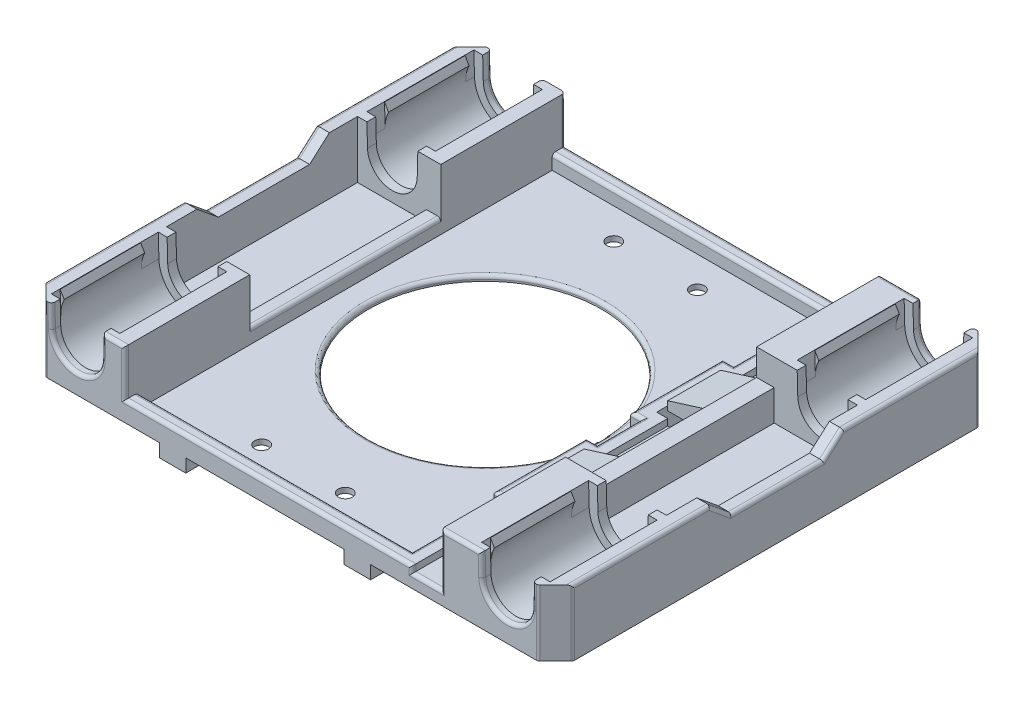
SolidWorks part; units mm, degrees
ref_plane "Front" through (0, 0, 0) normal (0, 0, 1) x (1, 0, 0)
ref_plane "Top" through (0, 0, 0) normal (0, 1, 0) x (1, 0, 0)
ref_plane "Right" through (0, 0, 0) normal (1, 0, 0) x (0, 0, -1)
sketch "Sketch1" plane through (0, 0, 0) normal (0, 1, 0) x (1, 0, 0)
  line L1 (-62.38, 50) -> (62.38, 50)
  line L2 (-62.38, 50) -> (-62.38, -50)
  line L3 (-62.38, -50) -> (62.38, -50)
  line L4 (62.38, 50) -> (62.38, -50)
  dimension "D1" = 124.76
  dimension "D2" = 100
  dimension "6" = 62.38
  dimension "D4" = 50
extrude "Boss-Extrude1" add sketch "Sketch1" along normal blind 20
sketch "Sketch2" plane through (0, 0, 50) normal (0, 0, 1) x (1, 0, 0)
  line L0 (-62.38, 0) -> (62.38, 0) construction
  line L1 (-62.38, 20) -> (-62.38, 0) construction
  line L2 (62.38, 20) -> (62.38, 0) construction
  circle A0 centre (-48.88, 10) radius 7.65
  circle A1 centre (48.88, 10) radius 7.65
  dimension "D2" = 15.3
  dimension "D3" = 15.3
  dimension "D1" = 13.5
  dimension "D4" = 10
  dimension "D5" = 10
  dimension "D6" = 13.5
  dimension "D7" = 97.76
extrude "Cut-Extrude1" cut sketch "Sketch2" against normal through all
sketch "Sketch4" plane through (-62.38, 0, 0) normal (-1, 0, 0) x (0, 0, 1)
  line L0 (-50, 20) -> (50, 20) construction
  line L1 (48, 2) -> (-48, 2)
  line L2 (48, 2) -> (48, 20)
  line L3 (48, 20) -> (-48, 20)
  line L4 (-48, 2) -> (-48, 20)
  line L5 (-50, 0) -> (50, 0) construction
  line L6 (50, 2.35) -> (50, 17.65) construction
  line L9 (-50, 20) -> (-50, 0) construction
  dimension "D1" = 2
  dimension "D2" = 2
  dimension "D3" = 2
extrude "Cut-Extrude2" cut sketch "Sketch4" against normal blind 21.26
sketch "Sketch5" plane through (62.38, 0, 0) normal (1, 0, 0) x (0, 0, -1)
  line L0 (-50, 20) -> (50, 20) construction
  line L1 (-48, 2) -> (48, 2)
  line L2 (-48, 2) -> (-48, 20)
  line L3 (-48, 20) -> (48, 20)
  line L4 (48, 2) -> (48, 20)
  line L5 (-50, 0) -> (50, 0) construction
  line L6 (-50, 20) -> (-50, 0) construction
  line L7 (50, 20) -> (50, 0) construction
  dimension "D1" = 2
  dimension "D2" = 2
  dimension "D3" = 2
extrude "Cut-Extrude3" cut sketch "Sketch5" against normal blind 24.5
sketch "Sketch6" plane through (0, 0, 48) normal (0, 0, -1) x (-1, 0, 0)
  line L0 (41.12, 20) -> (62.38, 20) construction
  line L1 (37.88, 20) -> (59.88, 20)
  line L2 (37.88, 20) -> (37.88, 2)
  line L3 (37.88, 2) -> (59.88, 2)
  line L4 (59.88, 20) -> (59.88, 2)
  line L5 (41.12, 2) -> (62.38, 2) construction
  circle A0 centre (48.88, 10) radius 7.65 construction
  circle A1 centre (48.88, 10) radius 7.65
  dimension "D1" = 22
  dimension "D2" = 11
extrude "Boss-Extrude2" add sketch "Sketch6" along normal blind 24.3
mirror "Mirror1" about plane through (0, 0, 0) normal (0, 0, 1) of "Boss-Extrude2"
mirror "Mirror2" about plane through (0, 0, 0) normal (1, 0, 0) of "Mirror1", "Boss-Extrude2"
sketch "Sketch7" plane through (0, 0, 50) normal (0, 0, 1) x (1, 0, 0)
  line L0 (41.2326, 9.8) -> (40.9659, 20)
  line L2 (-62.38, 20) -> (62.38, 20) construction
  line L3 (40.9659, 20) -> (56.7941, 20)
  line L4 (56.7941, 20) -> (56.5274, 9.8)
  circle A1 centre (48.88, 10) radius 7.65 construction
  arc A2 (41.2326, 9.8) -> (56.5274, 9.8) centre (48.88, 10) ccw
  dimension "D1" = 0.2
  dimension "D2" = 0.2
extrude "Cut-Extrude4" cut sketch "Sketch7" against normal blind 4
mirror "Mirror3" about plane through (0, 0, 0) normal (1, 0, 0) of "Cut-Extrude4"
mirror "Mirror4" about plane through (0, 0, 0) normal (0, 0, 1) of "Mirror3", "Cut-Extrude4"
sketch "Sketch8" plane through (0, 0, -23.7) normal (0, 0, 1) x (1, 0, 0)
  line L0 (56.5274, 9.8) -> (56.7941, 20) construction
  line L1 (40.9659, 20) -> (41.2326, 9.8) construction
  line L2 (56.5274, 9.8) -> (56.7941, 20)
  line L3 (40.9659, 20) -> (41.2326, 9.8)
  line L4 (56.7941, 20) -> (40.9659, 20)
  arc A0 (41.2326, 9.8) -> (56.5274, 9.8) centre (48.88, 10) ccw construction
  arc A1 (41.2326, 9.8) -> (56.5274, 9.8) centre (48.88, 10) ccw
extrude "Cut-Extrude5" cut sketch "Sketch8" against normal blind 4
mirror "Mirror5" about plane through (0, 0, 0) normal (1, 0, 0) of "Cut-Extrude5"
mirror "Mirror6" about plane through (0, 0, 0) normal (0, 0, 1) of "Mirror5", "Cut-Extrude5"
sketch "Sketch10" plane through (0, 0, -46) normal (0, 0, -1) x (-1, 0, 0)
  line L0 (41.0992, 14.9025) -> (41.9993, 13.3435)
  line L1 (56.5274, 9.8) -> (56.7941, 20) construction
  line L2 (56.6608, 14.9025) -> (56.7941, 20)
  line L3 (56.7941, 20) -> (40.9659, 20)
  line L4 (40.9659, 20) -> (41.0992, 14.9025)
  line L5 (40.9659, 20) -> (41.2326, 9.8) construction
  line L7 (55.7607, 13.3435) -> (56.6608, 14.9025)
  arc A0 (56.5274, 9.8) -> (41.2326, 9.8) centre (48.88, 10) ccw construction
  arc A1 (55.7607, 13.3435) -> (41.9993, 13.3435) centre (48.88, 10) ccw
  dimension "D2" = 151.498
  dimension "D1" = 151.498
extrude "Cut-Extrude6" cut sketch "Sketch10" against normal through all both and the other way through all
mirror "Mirror7" about plane through (0, 0, 0) normal (1, 0, 0) of "Cut-Extrude6"
ref_plane "Plane6" through (0, 10, 0) normal (0, 1, 0) x (1, 0, 0)
sketch "Sketch11" [suppressed] plane through (0, 10, 0) normal (0, 1, 0) x (1, 0, 0)
  line L4 (42.7319, -46) -> (42.7319, -27.7)
  line L5 (42.7319, -46) -> (42.7319, -27.7)
  line L6 (41.1969, -27.7) -> (41.1969, -46)
  line L7 (42.7319, -27.7) -> (41.1969, -27.7)
  line L8 (42.7319, -27.7) -> (41.1969, -27.7)
  line L9 (41.1969, -46) -> (42.7319, -46)
  line L10 (41.1969, -27.7) -> (41.1969, -46)
  line L11 (41.1969, -46) -> (42.7319, -46)
  line L12 (56.5631, -46) -> (56.5631, -27.7)
  line L13 (56.5631, -27.7) -> (55.0281, -27.7)
  line L14 (55.0281, -27.7) -> (55.0281, -46)
  line L15 (55.0281, -46) -> (56.5631, -46)
  line L16 (56.5631, -46) -> (56.5631, -27.7)
  line L17 (56.5631, -27.7) -> (55.0281, -27.7)
  line L18 (55.0281, -27.7) -> (55.0281, -46)
  line L19 (55.0281, -46) -> (56.5631, -46)
  dimension "D1" = 0
  dimension "D2" = 0
extrude "Cut-Extrude7" [suppressed] cut sketch "Sketch11" against normal through all
mirror "Mirror8" [suppressed] about plane through (0, 0, 0) normal (1, 0, 0)
mirror "Mirror9" [suppressed] about plane through (0, 0, 0) normal (0, 0, 1)
sketch "Sketch12" plane through (0, 0, -50) normal (0, 0, -1) x (-1, 0, 0)
  line L2 (54.7948, 20.0523) -> (62.38, 20)
  line L3 (62.38, 20) -> (62.38, 0)
  line L4 (42.9652, 20.0523) -> (43.2319, 9.8523)
  line L5 (54.5281, 9.8523) -> (54.7948, 20.0523)
  line L6 (42.9652, 20.0523) -> (43.2319, 9.8523)
  line L7 (54.5281, 9.8523) -> (54.7948, 20.0523)
  line L8 (62.38, 0) -> (30.8026, 0)
  line L9 (-62.38, 0) -> (62.38, 0) construction
  line L10 (30.8026, 0) -> (30.8026, 20)
  line L11 (-40.9659, 20) -> (40.9659, 20) construction
  line L12 (30.8026, 20) -> (42.9652, 20.0523)
  arc A2 (43.2319, 9.8523) -> (54.5281, 9.8523) centre (48.88, 10) ccw
  arc A3 (43.2319, 9.8523) -> (54.5281, 9.8523) centre (48.88, 10) ccw
  dimension "D1" = 2
extrude "Boss-Extrude3" add sketch "Sketch12" against normal blind 2
mirror "Mirror10" about plane through (0, 0, 0) normal (1, 0, 0) of "Boss-Extrude3"
mirror "Mirror11" about plane through (0, 0, 0) normal (0, 0, 1) of "Boss-Extrude3", "Mirror10"
sketch "Sketch13" plane through (0, 0, 23.7) normal (0, 0, -1) x (-1, 0, 0)
  line L0 (54.7948, 20.0523) -> (54.5281, 9.8523) construction
  line L1 (43.2319, 9.8523) -> (42.9652, 20.0523) construction
  line L2 (54.7948, 20.0523) -> (54.5281, 9.8523)
  line L3 (43.2319, 9.8523) -> (42.9652, 20.0523)
  line L4 (56.7941, 20) -> (54.7948, 20.0523)
  line L5 (56.7941, 20) -> (59.88, 20)
  line L6 (59.88, 20) -> (59.88, 2)
  line L7 (41.12, 2) -> (59.88, 2) construction
  line L8 (59.88, 2) -> (35.5, 2)
  line L9 (35.5, 2) -> (35.5, 20)
  line L11 (35.5, 20) -> (42.9652, 20.0523)
  arc A0 (43.2319, 9.8523) -> (54.5281, 9.8523) centre (48.88, 10) ccw construction
  arc A1 (43.2319, 9.8523) -> (54.5281, 9.8523) centre (48.88, 10) ccw
extrude "Boss-Extrude4" add sketch "Sketch13" along normal blind 2
mirror "Mirror12" about plane through (0, 0, 0) normal (1, 0, 0) of "Boss-Extrude4"
mirror "Mirror13" about plane through (0, 0, 0) normal (0, 0, 1) of "Mirror12", "Boss-Extrude4"
sketch "Sketch14" plane through (0, 0, 0) normal (0, -1, 0) x (1, 0, 0)
  line L0 (59.88, 21.7) -> (59.88, 48) construction
  line L1 (59.88, -50) -> (59.88, 50)
  line L2 (-62.38, 50) -> (62.38, 50) construction
  line L3 (62.38, 50) -> (62.38, -50) construction
  line L4 (62.38, 50) -> (62.38, -50)
  line L5 (59.88, 50) -> (62.38, 50)
  line L6 (59.88, -50) -> (62.38, -50)
extrude "Cut-Extrude9" cut sketch "Sketch14" against normal through all
mirror "Mirror15" about plane through (0, 0, 0) normal (1, 0, 0) of "Cut-Extrude9"
sketch "Sketch15" plane through (0, 20, 0) normal (0, 1, 0) x (1, 0, 0)
  line L0 (33.88, -50) -> (33.88, 50)
  line L1 (-30.8026, -50) -> (30.8026, -50) construction
  line L2 (30.8026, 50) -> (-30.8026, 50) construction
  line L3 (59.88, -21.7) -> (59.88, 21.7) construction
  line L4 (27.38, -50) -> (27.38, 50)
  line L5 (27.38, 50) -> (33.88, 50)
  line L6 (33.88, -50) -> (27.38, -50)
  dimension "D1" = 26
  dimension "D2" = 6.5
extrude "Cut-Extrude10" cut sketch "Sketch15" against normal blind 17
sketch "Sketch16" plane through (0, 2, 0) normal (0, 1, 0) x (1, 0, 0)
  line L2 (-59.88, 21.7) -> (-59.88, -21.7)
  line L3 (-59.88, -21.7) -> (-56.7941, -21.7)
  line L4 (-41.12, -21.7) -> (-59.88, -21.7) construction
  line L5 (-59.88, 21.7) -> (-56.7941, 21.7)
  line L6 (-56.7941, 23.7) -> (-56.7941, 48) construction
  line L7 (-56.7941, -21.7) -> (-56.7941, 21.7)
extrude "Boss-Extrude6" add sketch "Sketch16" along normal up to vertex (18 mm away)
mirror "Mirror16" about plane through (0, 0, 0) normal (1, 0, 0) of "Boss-Extrude6"
sketch "Sketch17" plane through (59.88, 0, 0) normal (1, 0, 0) x (0, 0, -1)
  line L0 (20.9433, 20) -> (10.8, 11)
  line L1 (10.8, 11) -> (-9.9399, 11)
  line L2 (-9.9399, 11) -> (-20.9009, 20)
  line L3 (48, 20) -> (-48, 20) construction
  line L4 (50, 10) -> (-50, 10) construction
  line L5 (20.9433, 20) -> (-20.9009, 20)
  dimension "D1" = 1
extrude "Cut-Extrude11" cut sketch "Sketch17" against normal blind 16
mirror "Mirror17" about plane through (0, 0, 0) normal (1, 0, 0) of "Cut-Extrude11"
sketch "Sketch18" plane through (0, 0, 0) normal (0, -1, 0) x (1, 0, 0)
  line L1 (24.88, 8) -> (24.88, 23)
  line L2 (33.88, 50) -> (33.88, -50) construction
  line L3 (33.88, 23) -> (33.88, 8)
  line L5 (33.88, 23) -> (24.88, 23)
  line L6 (50, 0) -> (-50, 0) construction
  line L7 (24.88, 8) -> (33.88, 8)
  dimension "D1" = 23
  dimension "D2" = 15
  dimension "D3" = 9
extrude "Cut-Extrude12" cut sketch "Sketch18" against normal blind 25
mirror "Mirror18" about plane through (0, 0, 0) normal (0, 0, 1) of "Cut-Extrude12"
sketch "Sketch19" plane through (33.88, 0, 0) normal (-1, 0, 0) x (0, 0, 1)
  line L0 (-8, 0) -> (-23, 0) construction
  line L1 (-21.5, 6.5) -> (-9.5, 6.5)
  line L2 (-21.5, 6.5) -> (-21.5, 4.5)
  line L3 (-21.5, 4.5) -> (-9.5, 4.5)
  line L4 (-9.5, 6.5) -> (-9.5, 4.5)
  line L5 (-8, 3) -> (-8, 0) construction
  line L6 (-23, 3) -> (-23, 0) construction
  dimension "D1" = 4.5
  dimension "D2" = 2
  dimension "D3" = 1.5
  dimension "D4" = 1.5
extrude "Boss-Extrude7" add sketch "Sketch19" along normal blind 8
mirror "Mirror19" about plane through (0, 0, 0) normal (0, 0, 1) of "Boss-Extrude7"
sketch "Sketch21" plane through (0, 20, 0) normal (0, 1, 0) x (1, 0, 0)
  line L2 (-41.12, 21.7) -> (-41.12, -21.7) construction
  line L6 (27.38, 50) -> (-30.8026, 50) construction
  circle A0 centre (-6.12, 0) radius 26.5
  dimension "D1" = 53
  dimension "D2" = 35
  dimension "D3" = 50
extrude "Cut-Extrude13" cut sketch "Sketch21" against normal through all
sketch "Sketch23" plane through (0, 0, 50) normal (0, 0, 1) x (1, 0, 0)
  line L0 (-59.88, 20.5) -> (59.88, 20.5)
  line L2 (-59.88, 0) -> (59.88, 0) construction
  line L3 (59.88, 15) -> (-59.88, 15)
  line L4 (59.88, 20.0172) -> (59.88, 0) construction
  line L6 (-59.88, 20.0172) -> (-59.88, 0) construction
  line L7 (-59.88, 15) -> (-59.88, 20.5)
  line L8 (59.88, 15) -> (59.88, 20.5)
  dimension "D1" = 15
extrude "Cut-Extrude18" cut sketch "Sketch23" against normal through all
sketch "Sketch26" plane through (0, 15, 0) normal (0, 1, 0) x (1, 0, 0)
  line L0 (-43.0973, 50) -> (27.38, 50) construction
  line L1 (27.38, -50) -> (-37.885, -50)
  line L2 (27.38, -50) -> (27.38, 50)
  line L3 (27.38, 50) -> (-37.885, 50)
  line L4 (-37.885, -50) -> (-37.885, 50)
extrude "Cut-Extrude19" cut sketch "Sketch26" against normal blind 6.02
sketch "Sketch27" plane through (-37.885, 0, 0) normal (1, 0, 0) x (0, 0, -1)
  line L0 (-21.7, 14.8665) -> (-21.7, 2) construction
  line L1 (21.7, 2) -> (21.7, 14.8665) construction
  line L2 (-21.7, 15) -> (-21.7, 8.98)
  line L3 (21.7, 8.98) -> (21.7, 15)
  line L4 (50, 15) -> (-50, 15) construction
  line L5 (21.7, 15) -> (-21.7, 15)
  line L6 (50, 8.98) -> (-50, 8.98) construction
  line L8 (21.7, 8.98) -> (-21.7, 8.98)
extrude "Cut-Extrude20" cut sketch "Sketch27" against normal blind 6
sketch "Sketch28" plane through (37.88, 0, 0) normal (1, 0, 0) x (0, 0, -1)
  line L0 (21.7, 2) -> (21.7, 15) construction
  line L1 (-21.7, 15) -> (21.7, 15)
  line L2 (-21.7, 15) -> (-21.7, 8.98)
  line L3 (-21.7, 8.98) -> (21.7, 8.98)
  line L4 (21.7, 15) -> (21.7, 8.98)
  dimension "D1" = 6.02
extrude "Cut-Extrude21" cut sketch "Sketch28" against normal blind 6
sketch "Sketch31" plane through (0, 8.98, 0) normal (0, 1, 0) x (1, 0, 0)
  line L0 (27.38, 23) -> (27.38, 50) construction
  line L1 (27.38, 50) -> (-37.885, 50) construction
  line L2 (-37.885, 50) -> (-37.885, 21.7) construction
  line L3 (-41.12, 21.7) -> (-37.885, 21.7) construction
  line L4 (-41.12, 21.7) -> (-41.12, -21.7) construction
  line L5 (-41.12, -21.7) -> (-37.885, -21.7) construction
  line L6 (-37.885, -21.7) -> (-37.885, -50) construction
  line L7 (-37.885, -50) -> (27.38, -50) construction
  line L8 (27.38, -50) -> (27.38, -23) construction
  line L9 (27.38, -23) -> (24.88, -23) construction
  line L10 (24.88, -23) -> (24.88, -8) construction
  line L11 (27.38, -8) -> (27.38, 8) construction
  line L12 (24.88, -8) -> (27.38, -8) construction
  line L13 (24.88, 23) -> (24.88, 8) construction
  line L14 (24.88, 8) -> (27.38, 8) construction
  line L15 (27.38, 23) -> (24.88, 23) construction
  line L16 (27.38, 23) -> (27.38, 50)
  line L17 (27.38, 50) -> (-37.885, 50)
  line L18 (-37.885, 50) -> (-37.885, 21.7)
  line L19 (-41.12, 21.7) -> (-37.885, 21.7)
  line L20 (-41.12, 21.7) -> (-41.12, -21.7)
  line L21 (-41.12, -21.7) -> (-37.885, -21.7)
  line L22 (-37.885, -21.7) -> (-37.885, -50)
  line L23 (-37.885, -50) -> (27.38, -50)
  line L24 (27.38, -50) -> (27.38, -23)
  line L25 (27.38, -23) -> (24.88, -23)
  line L26 (24.88, -23) -> (24.88, -8)
  line L27 (27.38, -8) -> (27.38, 8)
  line L28 (24.88, -8) -> (27.38, -8)
  line L29 (24.88, 23) -> (24.88, 8)
  line L30 (24.88, 8) -> (27.38, 8)
  line L31 (27.38, 23) -> (24.88, 23)
extrude "Cut-Extrude25" cut sketch "Sketch31" against normal blind 4.48
sketch "Sketch29" plane through (0, 4.5, 0) normal (0, 1, 0) x (1, 0, 0)
  line L8 (-37.885, 47) -> (-37.885, -47)
  line L19 (24.38, 47) -> (24.38, 26)
  line L20 (24.38, 26) -> (21.88, 26)
  line L21 (21.88, 26) -> (21.88, 5)
  line L22 (21.88, 5) -> (24.38, 5)
  line L23 (24.38, 5) -> (24.38, -5)
  line L24 (24.38, -5) -> (21.88, -5)
  line L25 (21.88, -5) -> (21.88, -26)
  line L26 (21.88, -26) -> (24.38, -26)
  line L27 (24.38, -26) -> (24.38, -47)
  line L33 (-37.885, -47) -> (24.38, -47)
  line L35 (24.38, 47) -> (-37.885, 47)
  circle A1 centre (-6.12, 0) radius 26.5
  point P37 (27.38, 5)
  point P38 (24.38, 8)
  dimension "D1" = 53
extrude "Cut-Extrude23" cut sketch "Sketch29" against normal blind 3.3
sketch "Sketch30" plane through (0, 0, 0) normal (0, -1, 0) x (1, 0, 0)
  line L0 (-55.88, 50) -> (-59.88, 46)
  line L1 (-59.88, 50) -> (59.88, 50) construction
  line L2 (-59.88, 50) -> (-59.88, -50) construction
  line L3 (-59.88, 50) -> (-55.88, 50)
  line L4 (-59.88, 50) -> (-59.88, 46)
  dimension "D1" = 4
extrude "Cut-Extrude24" cut sketch "Sketch30" against normal through all
mirror "Mirror20" about plane through (0, 0, 0) normal (0, 0, 1) of "Cut-Extrude24"
mirror "Mirror21" about plane through (0, 0, 0) normal (1, 0, 0) of "Mirror20", "Cut-Extrude24"
fillet "Fillet3" radius 0.8 52 edges at (-37.885, 9.75, 50) (-37.885, 9.75, -50) (-5.2525, 4.5, 50) (-5.2525, 4.5, -50) (-6.12, 1.2, 26.5) (-6.7525, 4.5, -47) (-6.7525, 4.5, 47) (24.38, 4.5, 36.5) (23.13, 4.5, 26) (21.88, 4.5, 15.5) (23.13, 4.5, 5) (24.38, 4.5, 0) (23.13, 4.5, -5) (21.88, 4.5, -15.5) (23.13, 4.5, -26) (24.38, 4.5, -36.5) (-55.88, 7.5, 50) (-59.88, 7.5, 46) (-59.88, 15, -30.6541) (-55.88, 7.5, -50) (-59.88, 7.5, -46) (55.88, 7.5, 50) (59.88, 7.5, 46) (59.88, 15, -30.6541) (55.88, 7.5, -50) (59.88, 7.5, -46) (-48.88, 4.35, -50) (-43.1646, 12.4261, -50) (48.88, 4.35, -50) (43.1646, 12.4261, -50) (-48.88, 4.35, 50) (-43.1646, 12.4261, 50) (48.88, 4.35, 50) (43.1646, 12.4261, 50) (30.63, 3, 50) (33.88, 9, 50) (27.38, 3.75, 50) (30.63, 3, -50) (27.38, 3.75, -50) (33.88, 9, -50) (59.88, 11, -0.4301) (59.88, 13, -13.0541) (-59.88, 11, -0.4301) (-59.88, 13, -13.0541) (-59.88, 13, 12.3757) (59.88, 13, 12.3757) (54.5954, 12.4261, 50) (-54.5954, 12.4261, 50) (54.5954, 12.4261, -50) (-54.5954, 12.4261, -50) (-59.88, 15, 30.4057) (59.88, 15, 30.4057)
ref_plane "Plane7" through (33.88, 6.5, 9.5) normal (0, 0, 1) x (1, 0, 0)
sketch "Sketch32" plane through (33.88, 6.5, 9.5) normal (0, 0, 1) x (1, 0, 0)
  line L0 (-8, 0) -> (0, 2.48)
  line L1 (-8, 0) -> (0, 0) construction
  line L2 (0, 0) -> (0, 3.7007) construction
rib "Rib1" sketch "Sketch32" sketch "Sketch32" thickness 12 parameters "D1"=12
mirror "Mirror22" about plane through (0, 0, 0) normal (0, 0, 1) of "Rib1"
sketch "Sketch36" plane through (33.88, 0, 0) normal (-1, 0, 0) x (0, 0, 1)
  line L0 (15.0542, 4.14) -> (14.925, 4.5)
  line L1 (15.5, 4.5) -> (15.5, -6.0947) construction
  line L2 (21.5, 4.5) -> (9.5, 4.5) construction
  line L3 (15.9458, 4.14) -> (16.075, 4.5)
  line L4 (14.925, 4.5) -> (16.075, 4.5)
  arc A0 (15.0542, 4.14) -> (15.9458, 4.14) centre (15.5, 4.3) ccw
  dimension "D1" = 1.15
  dimension "D2" = 0.2
  dimension "D3" = 0.36
extrude "Boss-Extrude8" add sketch "Sketch36" along normal up to surface (8 mm away) up to face at (25.88, 5.5, 15.5)
pattern_linear "LPattern1" count 3 spacing 2 along (0, 0, 1) count 3 spacing 2 along (0, 0, -1) of "Boss-Extrude8"
mirror "Mirror23" about plane through (0, 0, 0) normal (0, 0, 1) of "LPattern1", "Boss-Extrude8"
sketch "Sketch37" plane through (0, 0, 0) normal (0, -1, 0) x (1, 0, 0)
  line L0 (-55.5486, 50) -> (55.5486, 50) construction
  line L1 (17.88, 50) -> (11.88, 50)
  line L2 (17.88, 50) -> (17.88, 44)
  line L3 (17.88, 44) -> (11.88, 44)
  line L4 (11.88, 50) -> (11.88, 44)
  line L5 (55.5486, -50) -> (-55.5486, -50) construction
  line L6 (-24.12, 50) -> (-30.12, 50)
  line L7 (-24.12, 50) -> (-24.12, 44)
  line L8 (-24.12, 44) -> (-30.12, 44)
  line L9 (-30.12, 50) -> (-30.12, 44)
  line L10 (17.88, -50) -> (11.88, -50)
  line L11 (17.88, -50) -> (17.88, -44)
  line L12 (17.88, -44) -> (11.88, -44)
  line L13 (11.88, -50) -> (11.88, -44)
  line L14 (59.88, 45.6686) -> (59.88, -45.6686) construction
  line L15 (-24.12, -50) -> (-30.12, -50)
  line L16 (-24.12, -50) -> (-24.12, -44)
  line L17 (-24.12, -44) -> (-30.12, -44)
  line L18 (-30.12, -50) -> (-30.12, -44)
  circle A0 centre (-6.12, 0) radius 26.5 construction
  dimension "D1" = 42
  dimension "D2" = 36
  dimension "D3" = 18
  dimension "D4" = 6
extrude "Boss-Extrude9" add sketch "Sketch37" along normal blind 3
sketch "Sketch38" plane through (0, 0, 0) normal (0, -1, 0) x (1, 0, 0)
  line L0 (59.88, 45.6686) -> (59.88, -45.6686) construction
  line L1 (48.43, 20) -> (43.43, 20)
  line L2 (48.43, 20) -> (48.43, 5)
  line L3 (48.43, 5) -> (43.43, 5)
  line L4 (43.43, 20) -> (43.43, 5)
  line L5 (-59.88, 45.6686) -> (-59.88, -45.6686) construction
  line L6 (-44.74, 10.5) -> (-49.24, 10.5)
  line L7 (-44.74, 10.5) -> (-44.74, -10.5)
  line L8 (-44.74, -10.5) -> (-49.24, -10.5)
  line L9 (-49.24, 10.5) -> (-49.24, -10.5)
  circle A0 centre (-6.12, 0) radius 26.5 construction
  dimension "D3" = 20
  dimension "D7" = 10.5
  dimension "D1" = 15
  dimension "D2" = 5
  dimension "D4" = 11.45
  dimension "D5" = 21
  dimension "D6" = 4.5
  dimension "D8" = 10.64
extrude "Boss-Extrude10" add sketch "Sketch38" along normal blind 3
sketch "Sketch39" plane through (0, 0, 0) normal (0, -1, 0) x (1, 0, 0)
  line L0 (-59.88, 45.6686) -> (-59.88, -45.6686) construction
  circle A0 centre (2.12, 40) radius 1.6
  circle A1 centre (-16.88, 40) radius 1.6
  circle A2 centre (2.12, -40) radius 1.6
  circle A3 centre (-16.88, -40) radius 1.6
  circle A4 centre (-6.12, 0) radius 26.5 construction
  dimension "D1" = 40
  dimension "D3" = 19
  dimension "D5" = 3.2
  dimension "D2" = 40
  dimension "D4" = 43
extrude "Cut-Extrude26" cut sketch "Sketch39" against normal up to next
